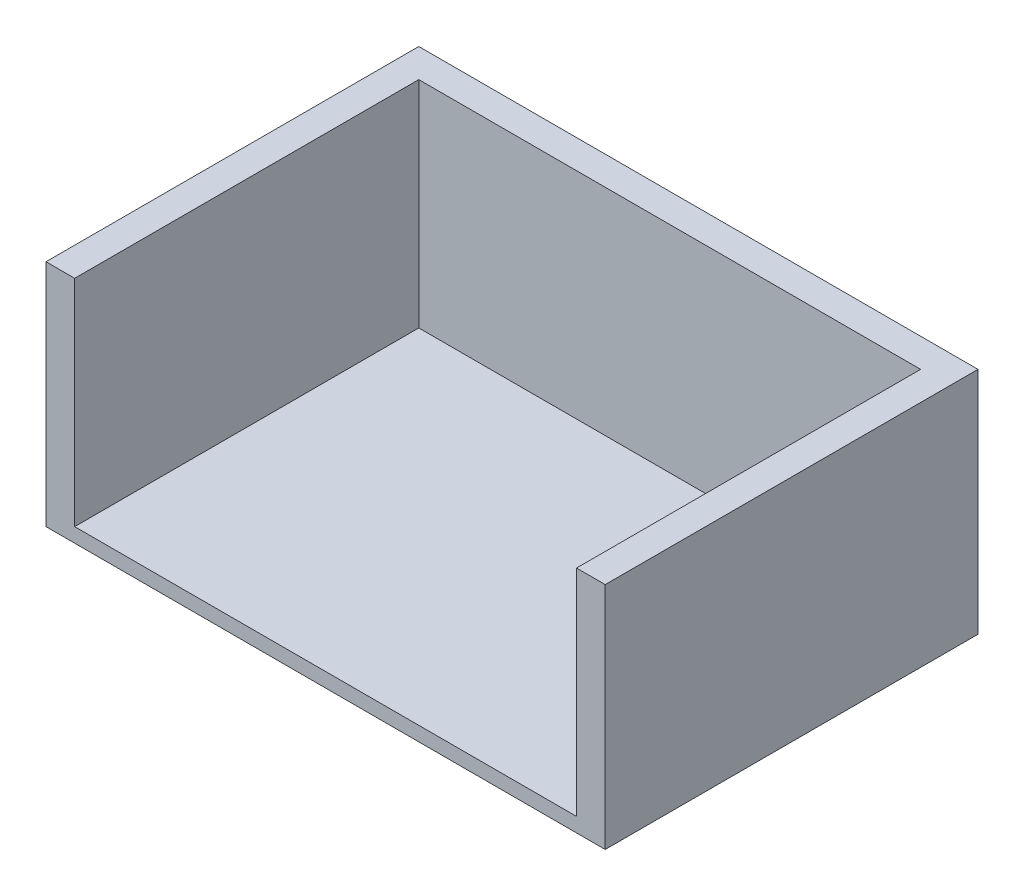
SolidWorks part; units mm, degrees
ref_plane "Front Plane" through (0, 0, 0) normal (0, 0, 1) x (1, 0, 0)
ref_plane "Top Plane" through (0, 0, 0) normal (0, 1, 0) x (1, 0, 0)
ref_plane "Right Plane" through (0, 0, 0) normal (1, 0, 0) x (0, 0, -1)
sketch "Sketch1" plane through (0, 0, 0) normal (0, 1, 0) x (1, 0, 0)
  line L0 (-195, 140) -> (-195, -120)
  line L1 (-175, 120) -> (175, 120)
  line L2 (-175, 120) -> (-175, -120)
  line L3 (-175, -120) -> (175, -120)
  line L4 (175, 120) -> (175, -120)
  line L5 (-175, 120) -> (175, -120) construction
  line L6 (-175, -120) -> (175, 120) construction
  line L7 (-195, -140) -> (195, -140) construction
  line L8 (195, 140) -> (195, -120)
  line L9 (-195, 140) -> (195, 140)
  line L10 (-175, -120) -> (-195, -120)
  line L11 (175, -120) -> (195, -120)
  line L13 (-195, -120) -> (-195, -140) construction
  line L14 (-195, 140) -> (-195, -140) construction
  line L15 (195, -120) -> (195, -140) construction
  line L16 (195, 140) -> (195, -140) construction
  point P0 (0, 0)
  dimension "D1" = 350
  dimension "D2" = 240
  dimension "D3" = 20
extrude "Boss-Extrude1" add sketch "Sketch1" along normal blind 150 contours L4 L11 L8 L9 L0 L10 L2 L1 region at (0, 0, -135.3128)
extrude "Boss-Extrude2" add sketch "Sketch1<3>" against normal blind 10 contours L4 L1 L2 L3 | L4 L11 L8 L9 L0 L10 L2 L1 region at (0, 0, -135.3128) region at (0, 0, 0)
sketch "Sketch1<3>" plane through (0, 0, 0) normal (0, 1, 0) x (1, 0, 0) same geometry as "Sketch1"
